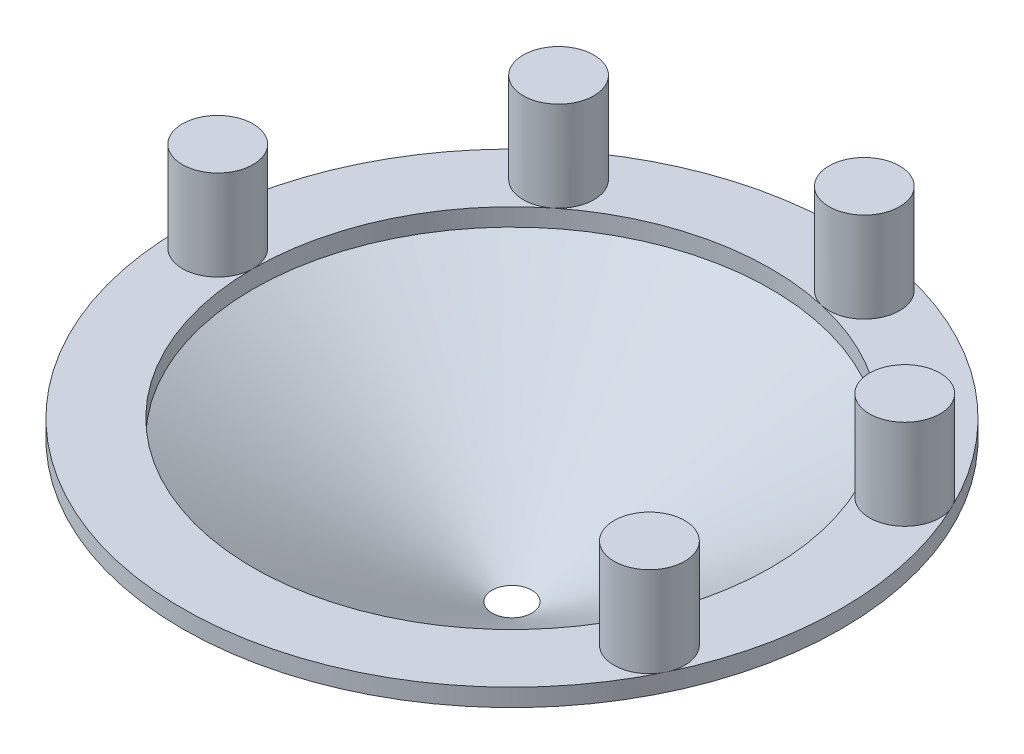
SolidWorks part; units mm, degrees
ref_plane "Front Plane" through (0, 0, 0) normal (0, 0, 1) x (1, 0, 0)
ref_plane "Top Plane" through (0, 0, 0) normal (0, 1, 0) x (1, 0, 0)
ref_plane "Right Plane" through (0, 0, 0) normal (1, 0, 0) x (0, 0, -1)
sketch "Sketch1" plane through (0, 0, 0) normal (0, 0, 1) x (1, 0, 0)
  line L0 (0, -582.4468) -> (0, 28539.8911) construction
  line L2 (28, 0) -> (3.175, -12)
  line L3 (3.175, -12) -> (1.686, -12)
  line L4 (1.686, -12) -> (22, 0)
  line L5 (1.686, -12) -> (0, -12) construction
  line L6 (22, 0) -> (0, 0) construction
  line L7 (22, 0) -> (22, 1.5)
  line L8 (22, 1.5) -> (28, 1.5)
  line L9 (28, 1.5) -> (28, 0)
  dimension "D1" = 1.489
  dimension "D2" = 1.686
  dimension "D3" = 22
  dimension "D4" = 6
  dimension "D5" = 12
  dimension "D6" = 1.5
revolve "Revolve1" add sketch "Sketch1" angle 360 about L0
sketch "Sketch3" plane through (0, 0, 0) normal (0, 1, 0) x (1, 0, 0)
  line L0 (-22, 0) -> (-28, 0) construction
  circle A1 centre (0, 0) radius 22 construction
  circle A2 centre (0, 0) radius 22 construction
  circle A3 centre (0, 0) radius 28 construction
  circle A4 centre (-25, 0) radius 3
extrude "Boss-Extrude1" add sketch "Sketch3" along normal blind 9.155
pattern_circular "CirPattern1" count 5 every 51.429 about axis through (0, 0, 0) along (0, -1, 0) of "Boss-Extrude1"
